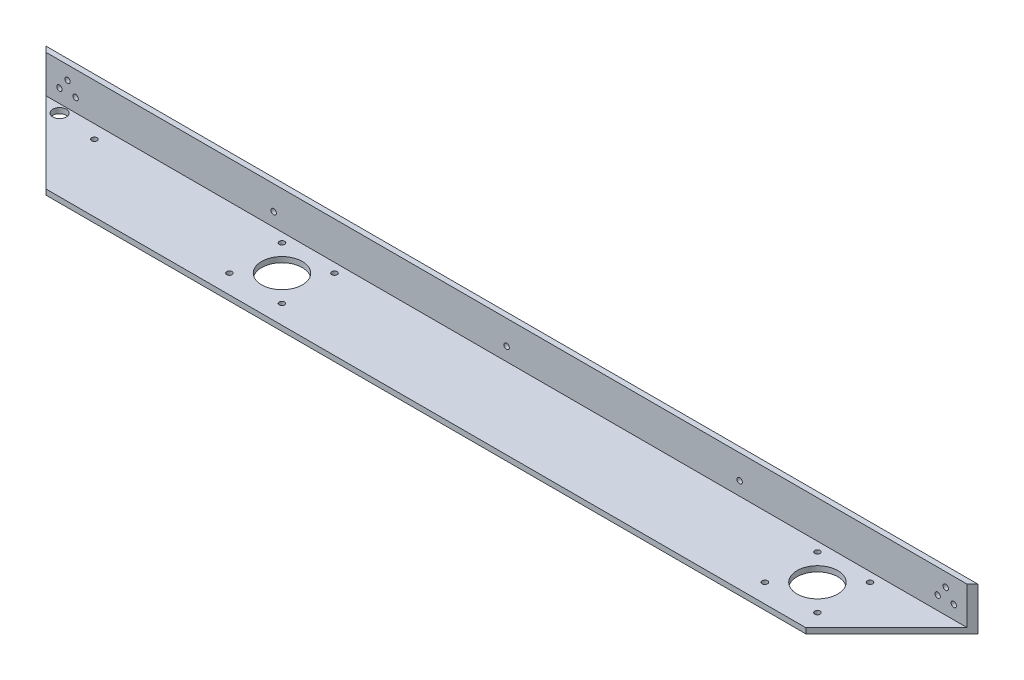
SolidWorks part; units mm, degrees
ref_plane "Front Plane" through (0, 0, 0) normal (0, 0, 1) x (1, 0, 0)
ref_plane "Top Plane" through (0, 0, 0) normal (0, 1, 0) x (1, 0, 0)
ref_plane "Right Plane" through (0, 0, 0) normal (1, 0, 0) x (0, 0, -1)
sketch "Sketch1" plane through (0, 0, 0) normal (1, 0, 0) x (0, 0, -1)
  line L0 (0, 0) -> (-50.8, 0)
  line L1 (-50.8, 0) -> (-50.8, 3.175)
  line L2 (-50.8, 3.175) -> (-3.175, 3.175)
  line L3 (-3.175, 3.175) -> (-3.175, 25.4)
  line L4 (-3.175, 25.4) -> (0, 25.4)
  line L5 (0, 25.4) -> (0, 0)
  dimension "LHeight" = 25.4
  dimension "LWidth" = 50.8
  dimension "LMaterialThickness" = 3.175
  dimension "D1" = 47.625
  dimension "D2" = 22.225
  dimension "D3" = 3.175
extrude "Boss-Extrude1" add sketch "Sketch1" along normal blind 550
chamfer "Chamfer7" distance 50.8 angle 45 1 edges at (0, 1.5875, 50.8)
chamfer "Chamfer8" distance 50.8 angle 45 1 edges at (550, 1.5875, 50.8)
sketch "BotthomHoles-Sketch2" plane through (0, 3.175, 0) normal (0, 1, 0) x (1, 0, 0)
  line L0 (546.825, -3.175) -> (3.175, -3.175) construction
  line L1 (550, 0) -> (0, 0) construction
  circle A0 centre (479.425, -24.175) radius 12
  circle A2 centre (463.925, -8.675) radius 1.5875
  circle A3 centre (494.925, -8.675) radius 1.5875
  circle A6 centre (463.925, -39.675) radius 1.5875
  circle A7 centre (494.925, -39.675) radius 1.5875
  circle A8 centre (39.6875, -11.1125) radius 1.5875
  circle A10 centre (178.925, -39.675) radius 1.5875
  circle A11 centre (147.925, -39.675) radius 1.5875
  circle A12 centre (178.925, -8.675) radius 1.5875
  circle A13 centre (147.925, -8.675) radius 1.5875
  circle A14 centre (163.425, -24.175) radius 12
  circle A15 centre (16, -8) radius 4
  point P32 (16.2737, -3.175)
  dimension "D9" = 3.175
  dimension "D10" = 24
  dimension "D13" = 3.175
  dimension "D14" = 8
  dimension "D2" = 8.675
  dimension "D5" = 15.5
  dimension "D6" = 31
  dimension "D7" = 15.5
  dimension "D8" = 31
  dimension "D11" = 21
  dimension "D3" = 70.575
  dimension "D4" = 11.1125
  dimension "D12" = 39.6875
  dimension "D15" = 31
  dimension "D16" = 15.5
  dimension "D17" = 316
  dimension "D18" = 8
  dimension "D19" = 16
extrude "BottomHoles-Cut-Extrude1" cut sketch "BotthomHoles-Sketch2" against normal through all
sketch "RightSideHoles-Sketch3" plane through (0, 0, 0) normal (0, 0, -1) x (-1, 0, 0)
  line L0 (-550, 0) -> (-550, 25.4) construction
  line L1 (0, 0) -> (0, 25.4) construction
  line L2 (-550, 25.4) -> (0, 25.4) construction
  circle A1 centre (-534.125, 17.4625) radius 1.5875
  circle A2 centre (-538.8875, 11.1125) radius 1.5875
  circle A3 centre (-529.3625, 11.1125) radius 1.5875
  circle A4 centre (-11.1125, 11.1125) radius 1.5875
  circle A5 centre (-20.6375, 11.1125) radius 1.5875
  circle A6 centre (-15.875, 17.4625) radius 1.5875
  circle A8 centre (-412.5, 11.1125) radius 1.5875
  circle A9 centre (-275, 11.1125) radius 1.5875
  circle A10 centre (-137.5, 11.1125) radius 1.5875
  dimension "D4" = 11.1125
  dimension "D7" = 3.175
  dimension "D2" = 15.875
  dimension "D6" = 15.875
  dimension "D8" = 137.5
  dimension "D9" = 137.5
  dimension "D10" = 137.5
  dimension "D5" = 11.1125
  dimension "D11" = 11.1125
  dimension "D3" = 7.9375
  dimension "D12" = 20.6375
  dimension "D13" = 20.6375
extrude "RightSideHoles-Cut-Extrude2" cut sketch "RightSideHoles-Sketch3" against normal through all
equation "\"LowerRailWidth\"= 2.00in"
equation "\"LowerRailHeight\"= 1.00in"
equation "\"RailThickness\"= .125in'Spec"
equation "\"SideRailHoleY1FromEdge\"= \"HoleOffsetFromEdge\""
equation "\"SideRailHoleX1FromSide\"= \"HoleOffsetFromSide\""
equation "\"StepperHoleDiameter\"= 24mm"
equation "\"StepperMountingHoleDiameter\"= 3.175mm"
equation "\"SideRailLength\"= 550mm"
equation "\"StepperMountingHoleDistance\"= 31mm'Spec"
equation "\"VSWidth\"= 1.25in'Spec"
equation "\"StepperMountingHoleOffsetFromLeftOrRightSide\"= \"StepperMountingHoleOffsetFromItsSide\" + \"RailThickness\""
equation "\"HoleOffsetFromEdge\"= \"RailThickness\" * 2.5"
equation "\"HoleOffsetFromSide\"= \"RailThickness\" * 3.5"
equation "\"StepperMountingHoleOffsetFromItsSide\"= 5.5mm'Spec"
equation "\"SideRailHoleX2FromSide\"= \"VSWidth\" - \"HoleOffsetFromEdge\" - \"RailThickness\"'Equals 20.6375"
equation "\"FasteningHoleDiameter\"= .125in"
equation "\"SideRailHoleY2FromSide\"= \"HoleOffsetFromSide\""
equation "\"LHeight@Sketch1\"=\"LowerRailHeight\""
equation "\"LWidth@Sketch1\"=\"LowerRailWidth\""
equation "\"D1@Chamfer7\"=\"LowerRailWidth\""
equation "\"D1@Chamfer8\"=\"LowerRailWidth\""
equation "\"D2@BotthomHoles-Sketch2\" = \"StepperMountingHoleOffsetFromLeftOrRightSide\""
equation "\"D5@BotthomHoles-Sketch2\" = \"StepperMountingHoleDistance\" / 2"
equation "\"D6@BotthomHoles-Sketch2\" = \"StepperMountingHoleDistance\""
equation "\"D7@BotthomHoles-Sketch2\" = \"StepperMountingHoleDistance\" / 2"
equation "\"D8@BotthomHoles-Sketch2\" = \"StepperMountingHoleDistance\""
equation "\"D9@BotthomHoles-Sketch2\" = \"StepperMountingHoleDiameter\""
equation "\"D10@BotthomHoles-Sketch2\" = \"StepperHoleDiameter\""
equation "\"D2@RightSideHoles-Sketch3\"=\"VSMidSideRailHoleXFromSideToCenter\" - \"RailThickness\""
equation "\"D4@RightSideHoles-Sketch3\" = \"SideRailHoleY2FromSide\""
equation "\"D7@RightSideHoles-Sketch3\" = \"FasteningHoleDiameter\""
equation "\"D1@Boss-Extrude1\"=\"SideRailLength\""
equation "\"D6@RightSideHoles-Sketch3\"=\"VSMidSideRailHoleXFromSideToCenter\" - \"RailThickness\""
equation "\"BedThirdSize\"= 70mm"
equation "\"BedInnerSquareWidth\"= \"BedThirdSize\" * 3'Equals 210"
equation "\"BedInnerSquareLength\"= \"BedInnerSquareWidth\""
equation "\"BedLWidth\"= \"BedThirdSize\"'Equals 70"
equation "\"BedLength\"= \"BedInnerSquareLength\" + \"BedLWidth\" * 2 + \"BedIncreasedByLength\"'Equals 350"
equation "\"DistanceBetweenFrontToBackStepperHoles\"= \"BedLength\" - \"DistanceFromBedFrontToFirstLeftStepperHole\"'Equals 316"
equation "\"D3@BotthomHoles-Sketch2\"=\"DistanceFromFrontSideToFirstLeftStepperHole\""
equation "\"DistanceFromBedFrontToFirstLeftStepperHole\"= \"LeadScrewNutPadSize\" + 10mm'Equals 34"
equation "\"DistanceFromFrontSideToBedFront\"= \"RailThickness\" + \"BeltTensionerDepth\" + 10mm'Equals 36.575"
equation "\"20TGT2PulleyDiameter\"= 17.9mm'Spec"
equation "\"BeltTensionerBackWallThickness\"= 4mm"
equation "\"BeltTensionerSpaceBetweenPulleyAndWall\"= 1.5mm"
equation "\"BeltTensionerInnerDepth\"= \"20TGT2PulleyDiameter\" + \"BeltTensionerSpaceBetweenPulleyAndWall\""
equation "\"BeltTensionerDepth\"= \"BeltTensionerBackWallThickness\" + \"BeltTensionerInnerDepth\"'Equals 23.4"
equation "\"BedIncreasedByLength\"= 0mm"
equation "\"LowerCornerBlockWidth\"= \"LowerRailWidth\" - \"RailThickness\" * 2'Room for left front stepper"
equation "\"D4@BotthomHoles-Sketch2\"=\"LowerCornerBlockY1FromSide\""
equation "\"D12@BotthomHoles-Sketch2\"=\"CornerEnclosureOffset\""
equation "\"D13@BotthomHoles-Sketch2\"=\"FasteningHoleDiameter\""
equation "\"CornerEnclosureOffset\"= \"LowerCornerBlockWidth\" - \"HoleOffsetFromEdge\" + \"RailThickness\""
equation "\"LowerCornerBlockY1FromSide\"= \"HoleOffsetFromSide\""
equation "\"D15@BotthomHoles-Sketch2\"=\"StepperMountingHoleDistance\""
equation "\"D16@BotthomHoles-Sketch2\"=\"StepperMountingHoleDistance\"/2"
equation "\"D17@BotthomHoles-Sketch2\"=\"DistanceBetweenFrontToBackStepperHoles\""
equation "\"DistanceFromFrontSideToFirstLeftStepperHole\"= \"DistanceFromFrontSideToBedFront\" + \"DistanceFromBedFrontToFirstLeftStepperHole\"'Equals 70.575"
equation "\"LeadScrewNutMountingHoleFlangeDiameter\"= 22mm'Spec"
equation "\"LeadScrewNutPadSize\"= \"LeadScrewNutMountingHoleFlangeDiameter\" + 2mm'Equals 24"
equation "\"LeftOrRightEnclosureOffsets\"= \"SideRailLength\" / 4"
equation "\"D8@RightSideHoles-Sketch3\"=\"LeftOrRightEnclosureOffsets\""
equation "\"D9@RightSideHoles-Sketch3\"=\"LeftOrRightEnclosureOffsets\""
equation "\"D10@RightSideHoles-Sketch3\"=\"LeftOrRightEnclosureOffsets\""
equation "\"D5@RightSideHoles-Sketch3\"=\"SideRailHoleX1FromSide\""
equation "\"D11@RightSideHoles-Sketch3\"=\"SideRailHoleX1FromSide\""
equation "\"D3@RightSideHoles-Sketch3\"=\"SideRailHoleY1FromEdge\""
equation "\"VSMidSideRailHoleXFromSideToCenter\"= \"RailThickness\" * 6"
equation "\"D12@RightSideHoles-Sketch3\"=\"SideRailHoleX2FromSide\""
equation "\"D13@RightSideHoles-Sketch3\"=\"SideRailHoleX2FromSide\""
equation "\"LowerRailCableHoleDiameter\"= 8mm"
equation "\"LowerRailCableHoleOffsetFromSide\"= 8mm"
equation "\"LowerRailCableHoleOffsetFromEdge\"= 16mm"
equation "\"D14@BotthomHoles-Sketch2\"=\"LowerRailCableHoleDiameter\""
equation "\"D18@BotthomHoles-Sketch2\"=\"LowerRailCableHoleOffsetFromSide\""
equation "\"D19@BotthomHoles-Sketch2\"=\"LowerRailCableHoleOffsetFromEdge\""
